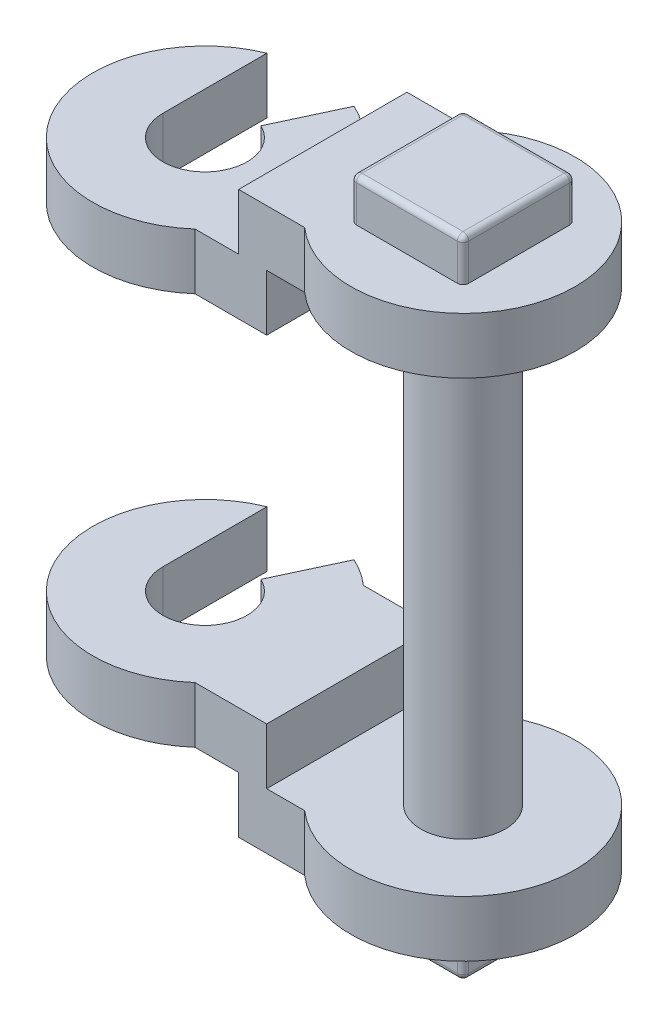
SolidWorks part; units mm, degrees
ref_plane "前视基准面" through (0, 0, 0) normal (0, 0, 1) x (1, 0, 0)
ref_plane "上视基准面" through (0, 0, 0) normal (0, 1, 0) x (1, 0, 0)
ref_plane "右视基准面" through (0, 0, 0) normal (1, 0, 0) x (0, 0, -1)
sketch "草图1" plane through (0, 0, 0) normal (0, 1, 0) x (1, 0, 0)
  circle A0 centre (0, 0) radius 0.75
extrude "凸台-拉伸1" add sketch "草图1" along normal blind 4 and the other way blind 4
sketch "草图2" plane through (0, 4, 0) normal (0, 1, 0) x (-1, 0, 0)
  circle A0 centre (0, 0) radius 2
extrude "凸台-拉伸2" add sketch "草图2" along normal blind 1
sketch "草图3" plane through (0, -4, 0) normal (0, -1, 0) x (1, 0, 0)
  circle A0 centre (0, 0) radius 2
extrude "凸台-拉伸3" add sketch "草图3" along normal blind 1
sketch "草图4" plane through (0, 5, 0) normal (0, 1, 0) x (-1, 0, 0)
  line L1 (-1, -1) -> (1, -1)
  line L2 (-1, -1) -> (-1, 1)
  line L3 (-1, 1) -> (1, 1)
  line L4 (1, -1) -> (1, 1)
extrude "凸台-拉伸4" add sketch "草图4" along normal blind 0.75
sketch "草图5" plane through (0, -5, 0) normal (0, -1, 0) x (1, 0, 0)
  line L1 (-1, -1) -> (1, -1)
  line L2 (-1, -1) -> (-1, 1)
  line L3 (-1, 1) -> (1, 1)
  line L4 (1, -1) -> (1, 1)
extrude "凸台-拉伸5" add sketch "草图5" along normal blind 0.75
sketch "草图6" plane through (0, 5, 0) normal (0, 1, 0) x (-1, 0, 0)
  line L1 (1, -1.5) -> (2.5, -1.5)
  line L2 (1, -1.5) -> (1, 1.5)
  line L3 (1, 1.5) -> (2.5, 1.5)
  line L4 (2.5, -1.5) -> (2.5, 1.5)
extrude "凸台-拉伸6" add sketch "草图6" against normal up to surface (1 mm away) up to face at (0, 4, 0.75)
sketch "草图7" plane through (0, -5, 0) normal (0, -1, 0) x (1, 0, 0)
  line L1 (-1, -1.5) -> (-2.5, -1.5)
  line L2 (-1, -1.5) -> (-1, 1.5)
  line L3 (-1, 1.5) -> (-2.5, 1.5)
  line L4 (-2.5, -1.5) -> (-2.5, 1.5)
extrude "凸台-拉伸8" add sketch "草图7" against normal up to surface (1 mm away) up to face at (0, -4, -0.75)
sketch "草图8" plane through (-2.5, 0, 0) normal (-1, 0, 0) x (0, 0, 1)
  line L1 (-1.5, 5) -> (1.5, 5)
  line L2 (-1.5, 5) -> (-1.5, 3)
  line L3 (-1.5, 3) -> (1.5, 3)
  line L4 (1.5, 5) -> (1.5, 3)
  line L5 (-1.5, -5) -> (1.5, -5)
  line L6 (-1.5, -5) -> (-1.5, -3)
  line L7 (-1.5, -3) -> (1.5, -3)
  line L8 (1.5, -5) -> (1.5, -3)
extrude "凸台-拉伸9" add sketch "草图8" against normal blind 0.5
sketch "草图9" plane through (0, 3, 0) normal (0, -1, 0) x (1, 0, 0)
  line L1 (-2.5, -1.5) -> (-3.2771, -1.5)
  line L2 (-2.5, -1.5) -> (-2.5, 1.5)
  line L3 (-2.5, 1.5) -> (-3.2771, 1.5)
  arc A0 (-3.2771, 1.5) -> (-3.2771, -1.5) centre (-4.6, 0) ccw
extrude "凸台-拉伸10" add sketch "草图9" against normal blind 1
extrude "凸台-拉伸11" add sketch "草图9<2>" along normal blind 1 from offset 6
sketch "草图9<2>" plane through (0, 3, 0) normal (0, -1, 0) x (1, 0, 0) same geometry as "草图9"
sketch "草图10" plane through (0, 4, 0) normal (0, 1, 0) x (-1, 0, 0)
  line L0 (5.35, 0) -> (5.35, -1.854)
  line L1 (4.283, -0.6797) -> (3.7548, -1.8126)
  arc A0 (5.35, 0) -> (4.283, -0.6797) centre (4.6, 0) ccw
  arc A1 (3.7548, -1.8126) -> (5.35, -1.854) centre (4.6, 0) ccw
extrude "切除-拉伸1" cut sketch "草图10" against normal through all
fillet "圆角1" radius 0.1 16 edges at (0, -5.75, 1) (1, -5.75, 0) (0, -5.75, -1) (-1, -5.75, 0) (0, 5.75, 1) (-1, 5.75, 0) (0, 5.75, -1) (1, 5.75, 0) (1, -5.375, 1) (1, -5.375, -1) (-1, -5.375, 1) (-1, -5.375, -1) (-1, 5.375, -1) (1, 5.375, -1) (-1, 5.375, 1) (1, 5.375, 1)
